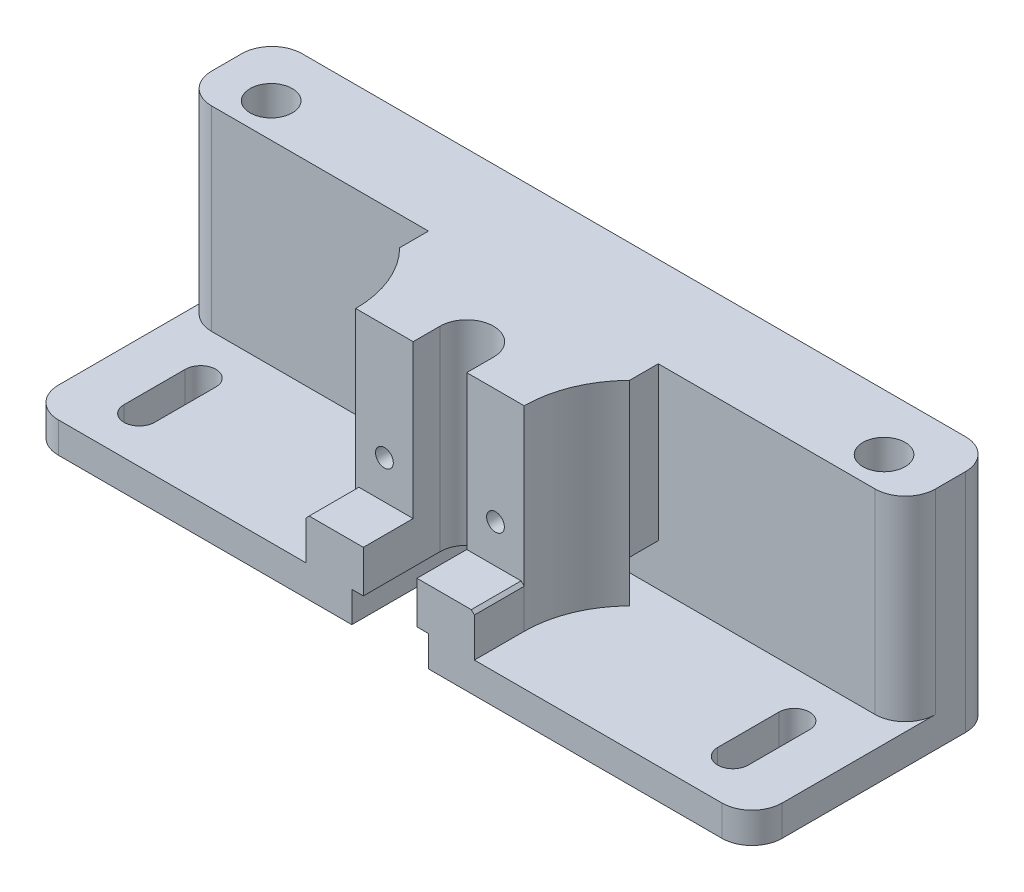
SolidWorks part; units mm, degrees
ref_plane "Front Plane" through (0, 0, 0) normal (0, 0, 1) x (1, 0, 0)
ref_plane "Top Plane" through (0, 0, 0) normal (0, 1, 0) x (1, 0, 0)
ref_plane "Right Plane" through (0, 0, 0) normal (1, 0, 0) x (0, 0, -1)
ref_plane "Plane1" through (0, 0, -20.6375) normal (0, 0, -1) x (-1, 0, 0)
sketch "Sketch1" plane through (0, 0, -20.6375) normal (0, 0, -1) x (-1, 0, 0)
  line L0 (19.05, 0) -> (19.05, 25.4)
  line L1 (19.05, 25.4) -> (-19.05, 25.4)
  line L2 (-19.05, 25.4) -> (-19.05, 0)
  line L3 (-19.05, 0) -> (19.05, 0)
extrude "Boss-Extrude1" add sketch "Sketch1" against normal blind 25.0825
ref_plane "Plane2" through (0, 0, -2.2225) normal (0, 0, 1) x (1, 0, 0)
sketch "Sketch6" plane through (0, 0, -2.2225) normal (0, 0, 1) x (1, 0, 0)
  line L0 (-6.0325, 8.1831) -> (-9.2075, 10.0162)
  line L1 (-9.2075, 10.0162) -> (-12.3825, 8.1831)
  line L2 (-12.3825, 8.1831) -> (-12.3825, 4.5169)
  line L3 (-12.3825, 4.5169) -> (-9.2075, 2.6838)
  line L4 (-9.2075, 2.6838) -> (-6.0325, 4.5169)
  line L5 (-6.0325, 4.5169) -> (-6.0325, 8.1831)
extrude "Cut-Extrude1" cut sketch "Sketch6" against normal blind 2.3876
sketch "Sketch12" plane through (0, 0, -2.2225) normal (0, 0, 1) x (1, 0, 0)
  line L0 (6.0325, 8.1831) -> (6.0325, 4.5169)
  line L1 (6.0325, 4.5169) -> (9.2075, 2.6838)
  line L2 (9.2075, 2.6838) -> (12.3825, 4.5169)
  line L3 (12.3825, 4.5169) -> (12.3825, 8.1831)
  line L4 (12.3825, 8.1831) -> (9.2075, 10.0162)
  line L5 (9.2075, 10.0162) -> (6.0325, 8.1831)
extrude "Cut-Extrude2" cut sketch "Sketch12" against normal blind 2.3876
ref_plane "Plane3" through (0, 0, 0) normal (0, -1, 0) x (-1, 0, 0)
sketch "Sketch18" plane through (0, 0, 0) normal (0, -1, 0) x (-1, 0, 0)
  line L0 (13.97, -4.445) -> (19.05, -4.445)
  line L1 (19.05, -4.445) -> (19.05, 7.9375)
  arc A0 (19.05, 7.9375) -> (13.97, -4.445) centre (31.6012, -4.445) ccw
extrude "Cut-Extrude3" cut sketch "Sketch18" against normal through all
sketch "Sketch19" plane through (0, 0, 0) normal (0, -1, 0) x (1, 0, 0)
  line L0 (4.445, 4.445) -> (-4.445, 4.445)
  line L1 (-4.445, 4.445) -> (-4.445, 0)
  line L2 (4.445, 0) -> (4.445, 4.445)
  arc A0 (-4.445, 0) -> (4.445, 0) centre (0, 0) ccw
extrude "Cut-Extrude4" cut sketch "Sketch19" against normal through all
sketch "Sketch20" plane through (0, 0, 0) normal (0, -1, 0) x (1, 0, 0)
  line L0 (19.05, -7.9375) -> (19.05, 4.445)
  line L1 (19.05, 4.445) -> (13.97, 4.445)
  arc A0 (13.97, 4.445) -> (19.05, -7.9375) centre (31.6012, 4.445) ccw
extrude "Cut-Extrude5" cut sketch "Sketch20" against normal through all
sketch "Sketch21" plane through (0, 0, 0) normal (0, -1, 0) x (1, 0, 0)
  line L0 (4.445, 0) -> (4.445, 12.7)
  line L1 (4.445, 12.7) -> (13.97, 12.7)
  line L2 (13.97, 12.7) -> (13.97, 4.445)
  line L3 (19.05, -7.9375) -> (-19.05, -7.9375)
  line L4 (-13.97, 4.445) -> (-13.97, 12.7)
  line L5 (-13.97, 12.7) -> (-4.445, 12.7)
  line L6 (-4.445, 12.7) -> (-4.445, 0)
  arc A0 (13.97, 4.445) -> (19.05, -7.9375) centre (31.6012, 4.445) ccw
  arc A1 (-19.05, -7.9375) -> (-13.97, 4.445) centre (-31.6012, 4.445) ccw
  arc A2 (-4.445, 0) -> (4.445, 0) centre (0, 0) ccw
extrude "Boss-Extrude2" add sketch "Sketch21" along normal blind 6.985
sketch "Sketch22" plane through (0, -6.985, 0) normal (0, -1, 0) x (1, 0, 0)
  line L0 (-4.445, -6.35) -> (4.445, -6.35)
  line L1 (4.445, -6.35) -> (4.445, 12.7)
  line L2 (4.445, 12.7) -> (60, 12.7)
  line L3 (60, 12.7) -> (60, -12.7)
  line L4 (60, -12.7) -> (-60, -12.7)
  line L5 (-60, -12.7) -> (-60, 12.7)
  line L6 (-60, 12.7) -> (-4.445, 12.7)
  line L7 (-4.445, 12.7) -> (-4.445, -6.35)
  point P8 (0, -12.7)
  dimension "D1" = 25.4
  dimension "D2" = 120
  dimension "D3" = 8.89
  dimension "D4" = 4.445
extrude "Boss-Extrude3" add sketch "Sketch22" along normal blind 5.08
ref_plane "Plane4" through (4.445, 0, 0) normal (-1, 0, 0) x (0, 0, 1)
sketch "Sketch29" plane through (4.445, 0, 0) normal (-1, 0, 0) x (0, 0, 1)
  line L0 (12.7, -6.985) -> (-6.35, -6.985)
  line L1 (-6.35, -6.985) -> (-6.35, -12.065)
  line L2 (-6.35, -12.065) -> (12.7, -12.065)
  line L3 (12.7, -12.065) -> (12.7, -6.985)
extrude "Cut-Extrude6" cut sketch "Sketch29" against normal blind 1.905
sketch "Sketch30" plane through (-4.445, 0, 0) normal (1, 0, 0) x (0, 0, -1)
  line L0 (-12.7, -6.985) -> (-12.7, -12.065)
  line L1 (-12.7, -12.065) -> (6.35, -12.065)
  line L2 (6.35, -12.065) -> (6.35, -6.985)
  line L3 (6.35, -6.985) -> (-12.7, -6.985)
extrude "Cut-Extrude7" cut sketch "Sketch30" against normal blind 1.905
ref_plane "Plane5" through (0, -12.065, 0) normal (0, -1, 0) x (-1, 0, 0)
sketch "Sketch48" plane through (0, -12.065, 0) normal (0, -1, 0) x (-1, 0, 0)
  line L0 (-51.7525, 5.08) -> (-51.7525, -5.08)
  line L1 (-46.6725, -5.08) -> (-46.6725, 5.08)
  arc A0 (-46.6725, 5.08) -> (-51.7525, 5.08) centre (-49.2125, 5.08) ccw
  arc A1 (-51.7525, -5.08) -> (-46.6725, -5.08) centre (-49.2125, -5.08) ccw
extrude "Cut-Extrude10" cut sketch "Sketch48" against normal up to next
sketch "Sketch57" plane through (0, -12.065, 0) normal (0, -1, 0) x (-1, 0, 0)
  line L0 (46.6725, 5.08) -> (46.6725, -5.08)
  line L1 (51.7525, -5.08) -> (51.7525, 5.08)
  arc A0 (51.7525, 5.08) -> (46.6725, 5.08) centre (49.2125, 5.08) ccw
  arc A1 (46.6725, -5.08) -> (51.7525, -5.08) centre (49.2125, -5.08) ccw
extrude "Cut-Extrude11" cut sketch "Sketch57" against normal up to next
ref_plane "Plane6" through (0, 6.35, 0) normal (0, 1, 0) x (1, 0, 0)
sketch "Sketch67" plane through (0, 6.35, 0) normal (0, 1, 0) x (1, 0, 0)
  line L0 (-7.7343, 20.6375) -> (-9.2075, 20.6375)
  line L1 (-9.2075, 20.6375) -> (-9.2075, 4.6101)
  line L2 (-9.2075, 4.6101) -> (-7.7343, 4.6101)
  line L3 (-7.7343, 4.6101) -> (-7.7343, 20.6375)
  line L4 (-9.2075, 20.6375) -> (-9.2075, 4.6101) construction
revolve "Cut-Revolve1" cut sketch "Sketch67" angle 360 about L1 reverse direction yes
sketch "Sketch77" plane through (0, 6.35, 0) normal (0, 1, 0) x (1, 0, 0)
  line L0 (10.6807, 20.6375) -> (9.2075, 20.6375)
  line L1 (9.2075, 20.6375) -> (9.2075, 4.6101)
  line L2 (9.2075, 4.6101) -> (10.6807, 4.6101)
  line L3 (10.6807, 4.6101) -> (10.6807, 20.6375)
  line L4 (9.2075, 20.6375) -> (9.2075, 4.6101) construction
revolve "Cut-Revolve2" cut sketch "Sketch77" angle 360 about L1 reverse direction yes
hole_wizard "M2.5 Clearance Hole1" positions "Sketch79" profile "Sketch78" hole size "M2.5" standard "ANSI Metric"
sketch "Sketch79" plane through (0, 0, 4.445) normal (0, 0, 1) x (1, 0, 0)
  point P0 (9.2075, 6.35)
  point P1 (-9.2075, 6.35)
sketch "Sketch78" plane through (9.2075, 6.35, 4.445) normal (1, 0, 0) x (0, -1, 0)
  line L0 (0, 0) -> (0, 25.0825)
  line L1 (0, 25.0825) -> (1.4732, 25.0825)
  line L2 (1.4732, 25.0825) -> (1.4732, 0)
  line L5 (1.4732, 0) -> (0, 0)
  line L11 (0, -6.35) -> (0, 107.95) construction
  dimension "Thru Hole Dia." = 2.9464
  dimension "Thru Hole Depth" = 25.0825
chamfer "Chamfer1" distance 0.5111 angle 45.61 1 edges at (13.97, 0, 8.5725) first distance on face at (13.97, -3.4925, 8.5725)
chamfer "Chamfer2" distance 0.5582 angle 43.977 1 edges at (-13.97, 0, 8.5725) first distance on face at (-13.97, -3.4925, 8.5725)
sketch "Sketch80" plane through (0, 0, -20.6375) normal (0, 0, -1) x (-1, 0, 0)
  line L0 (-19.05, 25.4) -> (19.05, 25.4)
  line L1 (-19.05, 25.4) -> (-19.05, 0)
  line L2 (-19.05, 0) -> (19.05, 0)
  line L3 (19.05, 25.4) -> (19.05, 0)
extrude "Cut-Extrude13" cut sketch "Sketch80" against normal up to surface (7.9375 mm away) up to face at (0, -9.525, -12.7)
sketch "Sketch81" plane through (0, 25.4, 0) normal (0, 1, 0) x (1, 0, 0)
  line L0 (-19.05, 12.7) -> (19.05, 12.7) construction
  line L1 (60, 12.7) -> (-60, 12.7)
  line L2 (60, 12.7) -> (60, 27.7)
  line L3 (60, 27.7) -> (-60, 27.7)
  line L4 (-60, 12.7) -> (-60, 27.7)
  line L5 (-60, 12.7) -> (60, 12.7) construction
  point P0 (0, 12.7)
  point P7 (0, 12.7)
  dimension "D1" = 120
  dimension "D2" = 15
extrude "Boss-Extrude4" add sketch "Sketch81" against normal up to surface (37.465 mm away) up to face at (-49.2125, -12.065, 0)
sketch "Sketch82" plane through (0, -12.065, 0) normal (0, -1, 0) x (1, 0, 0)
  line L0 (-42.1371, -18.379) -> (42.1371, -18.379) construction
  circle A0 centre (-50.8, -18.379) radius 3.5
  circle A1 centre (50.8, -18.379) radius 3.5
  point P3 (0, -18.379)
  point P7 (0, -18.379)
  dimension "D1" = 50.8
  dimension "D3" = 7
  dimension "D4" = 7
  dimension "D2" = 50.8
extrude "Cut-Extrude14" cut sketch "Sketch82" against normal through all
fillet "Fillet3" radius 5 2 edges at (60, 6.6675, -27.7) (-60, 6.6675, -27.7)
fillet "Fillet4" radius 5 2 edges at (-60, 9.2075, -12.7) (60, 9.2075, -12.7)
fillet "Fillet5" radius 5 2 edges at (60, -9.525, 12.7) (-60, -9.525, 12.7)
